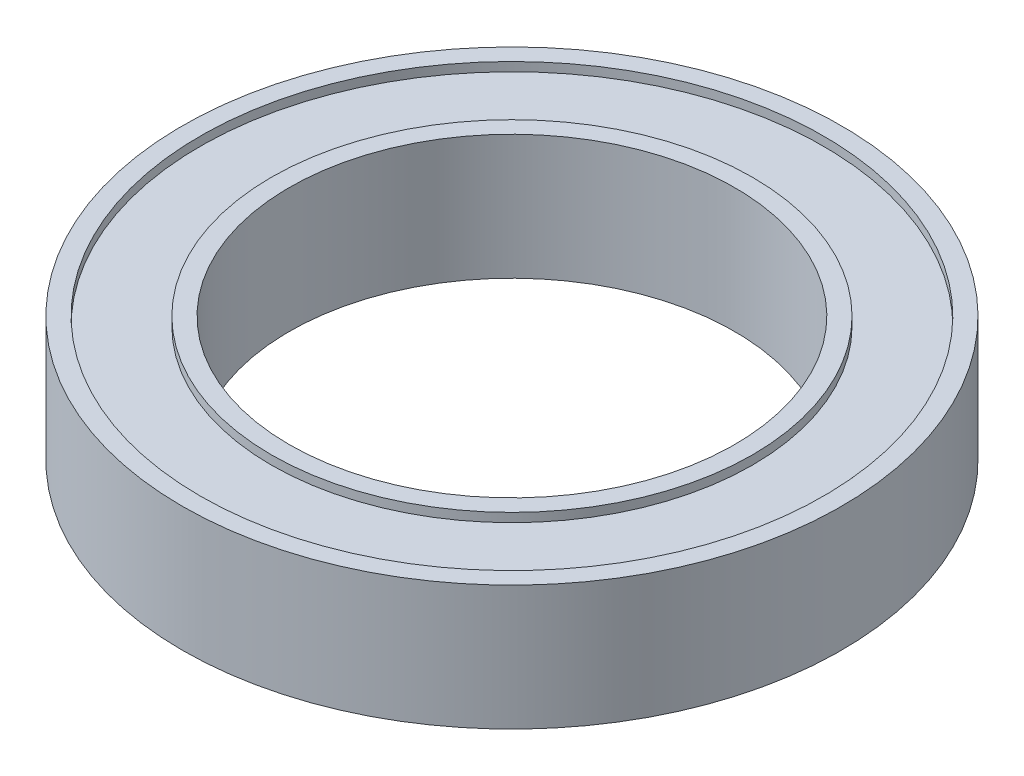
SolidWorks part; units mm, degrees
ref_plane "前视基准面" through (0, 0, 0) normal (0, 0, 1) x (1, 0, 0)
ref_plane "上视基准面" through (0, 0, 0) normal (0, 1, 0) x (1, 0, 0)
ref_plane "右视基准面" through (0, 0, 0) normal (1, 0, 0) x (0, 0, -1)
other "Configuration Table"
sketch "草图1" plane through (0, 0, 0) normal (0, 1, 0) x (1, 0, 0)
  circle A0 centre (0, 0) radius 12.5
  circle A1 centre (0, 0) radius 13.5
  circle A2 centre (0, 0) radius 17.5
  circle A3 centre (0, 0) radius 18.5
  dimension "D1" = 25
  dimension "D2" = 27
  dimension "D3" = 37
  dimension "D4" = 35
extrude "凸台-拉伸1" add sketch "草图1" along normal blind 3.5 and the other way blind 3.5 contours A3 A2 | A1 A0 region at (-13.1182, 0, 0) region at (-17.9767, 0, 0)
sketch "草图2" plane through (0, 0, 0) normal (0, 1, 0) x (1, 0, 0)
  circle A0 centre (0, 0) radius 13.5
  circle A1 centre (0, 0) radius 17.5
  circle A2 centre (0, 0) radius 13.5 construction
  circle A3 centre (0, 0) radius 17.5 construction
extrude "凸台-拉伸2" add sketch "草图2" along normal blind 3 and the other way blind 3
